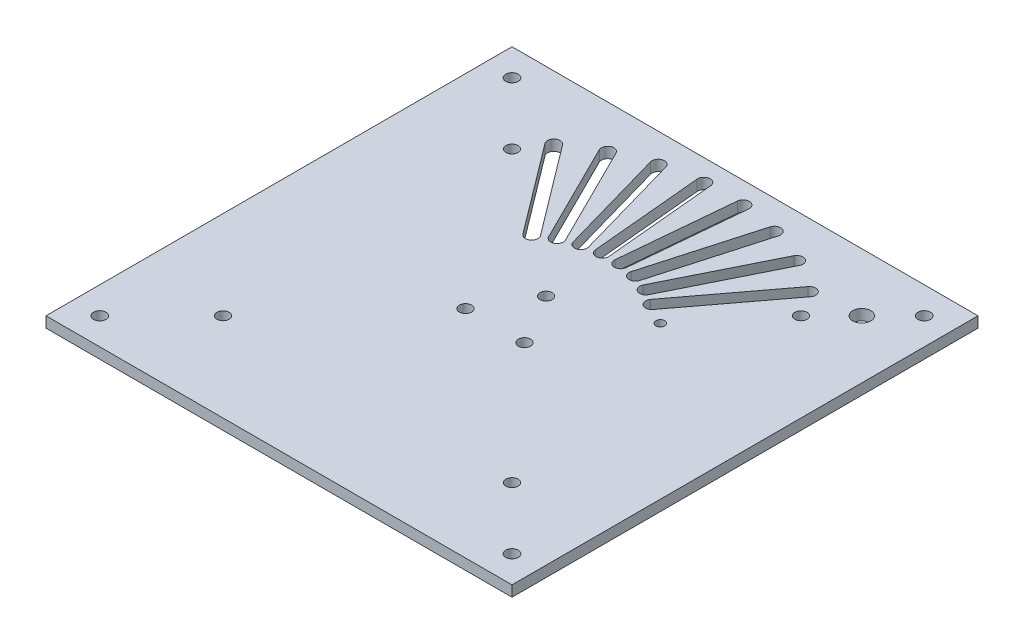
SolidWorks part; units mm, degrees
material "Acrylic (Medium-high impact)"
ref_plane "Front Plane" through (0, 0, 0) normal (0, 0, 1) x (1, 0, 0)
ref_plane "Top Plane" through (0, 0, 0) normal (0, 1, 0) x (1, 0, 0)
ref_plane "Right Plane" through (0, 0, 0) normal (1, 0, 0) x (0, 0, -1)
sketch "Sketch2" plane through (0, 0, 0) normal (0, 1, 0) x (1, 0, 0)
  line L1 (-65, -65) -> (65, -65)
  line L2 (-65, -65) -> (-65, 65)
  line L3 (-65, 65) -> (65, 65)
  line L4 (65, -65) -> (65, 65)
  line L5 (-65, -65) -> (65, 65) construction
  line L6 (-65, 65) -> (65, -65) construction
  point P0 (0, 0)
  dimension "D1" = 130
  dimension "D2" = 130
extrude "Boss-Extrude1" add sketch "Sketch2" along normal blind 3
sketch "Sketch4" plane through (0, 3, 0) normal (0, 1, 0) x (1, 0, 0)
  line L8 (57.5, -57.5) -> (57.5, 57.5)
  line L9 (57.5, 57.5) -> (-57.5, 57.5)
  line L10 (-57.5, 57.5) -> (-57.5, -57.5)
  line L11 (-57.5, -57.5) -> (57.5, -57.5)
  line L12 (57.5, -57.5) -> (57.5, 57.5) construction
  line L13 (57.5, 57.5) -> (-57.5, 57.5) construction
  line L14 (-57.5, 57.5) -> (-57.5, -57.5) construction
  line L15 (-57.5, -57.5) -> (57.5, -57.5) construction
  circle A0 centre (-57.5, 57.5) radius 1.75
  circle A1 centre (57.5, 57.5) radius 1.75
  circle A2 centre (57.5, -57.5) radius 1.75
  circle A3 centre (-57.5, -57.5) radius 1.75
  dimension "D2" = 3.5
  dimension "D1" = 7.5
extrude "Cornerpiece holes" cut sketch "Sketch4" against normal up to next
sketch "Sketch6" plane through (0, 3, 0) normal (0, 1, 0) x (1, 0, 0)
  line L6 (-40.3051, -40.3051) -> (40.3051, -40.3051) construction
  line L7 (-40.3051, -40.3051) -> (-40.3051, 40.3051) construction
  line L8 (-40.3051, 40.3051) -> (40.3051, 40.3051) construction
  line L9 (40.3051, -40.3051) -> (40.3051, 40.3051) construction
  line L10 (-40.3051, -40.3051) -> (40.3051, 40.3051) construction
  line L11 (-40.3051, 40.3051) -> (40.3051, -40.3051) construction
  circle A4 centre (-40.3051, 40.3051) radius 1.7
  circle A5 centre (40.3051, 40.3051) radius 1.7
  circle A6 centre (40.3051, -40.3051) radius 1.7
  circle A7 centre (-40.3051, -40.3051) radius 1.7
  point P0 (0, 0)
  dimension "D2" = 3.4
  dimension "D1" = 57
extrude "Cut-Extrude2" cut sketch "Sketch6" against normal up to next
sketch "Sketch8" plane through (0, 3, 0) normal (0, 1, 0) x (1, 0, 0)
  circle A4 centre (0, 9.5) radius 1.7
  circle A5 centre (8.2272, -4.75) radius 1.7
  circle A6 centre (-8.2272, -4.75) radius 1.7
  point P9 (0, 0)
  dimension "D1" = 9.5
  dimension "D3" = 3.4
  dimension "D2" = 3
extrude "Cut-Extrude3" cut sketch "Sketch8" against normal up to next
sketch "Sketch9" plane through (0, 3, 0) normal (0, 1, 0) x (1, 0, 0)
  line L0 (65, -65) -> (65, 65) construction
  line L1 (48.7904, 48.7904) -> (0, 0) construction
  line L2 (0, 0) -> (50000, 0) construction
  circle A0 centre (0, 0) radius 65 construction
  circle A1 centre (48.7904, 48.7904) radius 2.5
  dimension "D3" = 4
  dimension "D1" = 5
  dimension "D2" = 45
extrude "Primary wire hole" cut sketch "Sketch9" against normal up to next
sketch "Sketch10" plane through (0, 3, 0) normal (0, 1, 0) x (1, 0, 0)
  line L0 (0, 0) -> (22.5064, 18.8851) construction
  line L1 (0, 0) -> (50000, 0) construction
  circle A0 centre (0, 0) radius 24.13 construction
  circle A1 centre (22.5064, 18.8851) radius 1.25
  dimension "D1" = 48.26
  dimension "D3" = 2.5
  dimension "D2" = 40
  dimension "D4" = 4
extrude "Secondary wire hole" cut sketch "Sketch10" against normal up to next
sketch "Sketch11" plane through (0, 3, 0) normal (0, 1, 0) x (1, 0, 0)
  line L0 (-35.6575, 47.3192) -> (-16.7786, 22.266) construction
  line L1 (-34.2599, 48.3723) -> (-15.381, 23.3191)
  line L2 (-37.0552, 46.266) -> (-18.1762, 21.2128)
  line L3 (0, 0) -> (-16.7786, 22.266) construction
  line L4 (-27.9382, 52.2789) -> (-13.976, 24.1874)
  line L5 (-24.804, 53.8367) -> (-10.8418, 25.7452)
  line L6 (-26.3711, 53.0578) -> (-12.4089, 24.9663) construction
  line L7 (-17.8729, 56.5171) -> (-9.3013, 26.3409)
  line L8 (-14.5061, 57.4735) -> (-5.9345, 27.2972)
  line L9 (-16.1895, 56.9953) -> (-7.6179, 26.8191) construction
  line L10 (-7.2008, 58.8368) -> (-4.3109, 27.6002)
  line L11 (-3.7157, 59.1593) -> (-0.8258, 27.9227)
  line L12 (-5.4582, 58.9981) -> (-2.5684, 27.7614) construction
  line L13 (3.7157, 59.1593) -> (0.8258, 27.9227)
  line L14 (7.2008, 58.8368) -> (4.3109, 27.6002)
  line L15 (5.4582, 58.9981) -> (2.5684, 27.7614) construction
  line L18 (0, 0) -> (50000, 0) construction
  line L19 (14.5061, 57.4735) -> (5.9345, 27.2972)
  line L20 (17.8729, 56.5171) -> (9.3013, 26.3409)
  line L21 (16.1895, 56.9953) -> (7.6179, 26.8191) construction
  line L22 (24.804, 53.8367) -> (10.8418, 25.7452)
  line L23 (27.9382, 52.2789) -> (13.976, 24.1874)
  line L24 (26.3711, 53.0578) -> (12.4089, 24.9663) construction
  line L25 (34.2599, 48.3723) -> (15.381, 23.3191)
  line L26 (37.0552, 46.266) -> (18.1762, 21.2128)
  line L27 (35.6575, 47.3192) -> (16.7786, 22.266) construction
  line L28 (0, 0) -> (16.7786, 22.266) construction
  circle A0 centre (0, 0) radius 24.13 construction
  circle A1 centre (0, 0) radius 63 construction
  arc A2 (-34.2599, 48.3723) -> (-37.0552, 46.266) centre (-35.6575, 47.3192) ccw
  arc A3 (-18.1762, 21.2128) -> (-15.381, 23.3191) centre (-16.7786, 22.266) ccw
  arc A4 (-24.804, 53.8367) -> (-27.9382, 52.2789) centre (-26.3711, 53.0578) ccw
  arc A5 (-13.976, 24.1874) -> (-10.8418, 25.7452) centre (-12.4089, 24.9663) ccw
  arc A6 (-14.5061, 57.4735) -> (-17.8729, 56.5171) centre (-16.1895, 56.9953) ccw
  arc A7 (-9.3013, 26.3409) -> (-5.9345, 27.2972) centre (-7.6179, 26.8191) ccw
  arc A8 (-3.7157, 59.1593) -> (-7.2008, 58.8368) centre (-5.4582, 58.9981) ccw
  arc A9 (-4.3109, 27.6002) -> (-0.8258, 27.9227) centre (-2.5684, 27.7614) ccw
  arc A10 (7.2008, 58.8368) -> (3.7157, 59.1593) centre (5.4582, 58.9981) ccw
  arc A11 (0.8258, 27.9227) -> (4.3109, 27.6002) centre (2.5684, 27.7614) ccw
  arc A14 (17.8729, 56.5171) -> (14.5061, 57.4735) centre (16.1895, 56.9953) ccw
  arc A15 (5.9345, 27.2972) -> (9.3013, 26.3409) centre (7.6179, 26.8191) ccw
  arc A16 (27.9382, 52.2789) -> (24.804, 53.8367) centre (26.3711, 53.0578) ccw
  arc A17 (10.8418, 25.7452) -> (13.976, 24.1874) centre (12.4089, 24.9663) ccw
  arc A18 (37.0552, 46.266) -> (34.2599, 48.3723) centre (35.6575, 47.3192) ccw
  arc A19 (15.381, 23.3191) -> (18.1762, 21.2128) centre (16.7786, 22.266) ccw
  point P6 (-26.2181, 34.7926)
  point P17 (-19.39, 39.012)
  point P24 (-11.9037, 41.9072)
  point P31 (-4.0133, 43.3797)
  point P36 (0, 0)
  point P38 (4.0133, 43.3797)
  point P48 (11.9037, 41.9072)
  point P55 (19.39, 39.012)
  point P62 (26.2181, 34.7926)
  dimension "D1" = 48.26
  dimension "D2" = 126
  dimension "D4" = 2
  dimension "D5" = 3.5
  dimension "D7" = 53
  dimension "D8" = 53
  dimension "D6" = 8
extrude "Cut-Extrude6" cut sketch "Sketch11" against normal up to next
equation "\"D1@Sketch4\"=4.50+3"
equation "\"D1@Sketch10\"=1.9in"
equation "\"D1@Sketch11\"=1.9in"
equation "\"D2@Sketch11\"=130mm-2*2mm"
